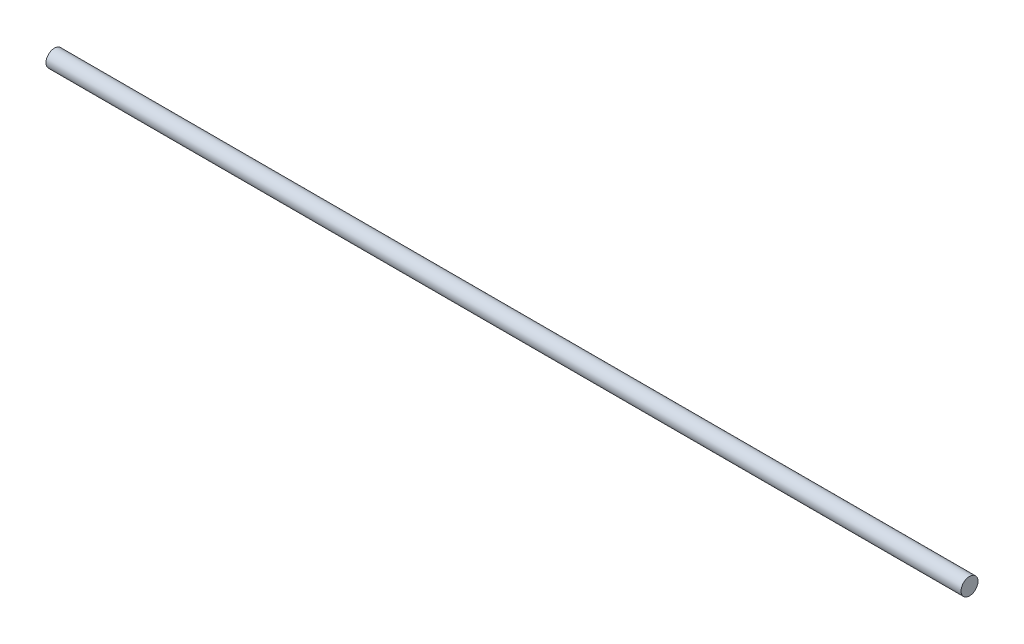
SolidWorks part; units mm, degrees
ref_plane "Front Plane" through (0, 0, 0) normal (0, 0, 1) x (1, 0, 0)
ref_plane "Top Plane" through (0, 0, 0) normal (0, 1, 0) x (1, 0, 0)
ref_plane "Right Plane" through (0, 0, 0) normal (1, 0, 0) x (0, 0, -1)
sketch "Sketch1" plane through (0, 0, 0) normal (1, 0, 0) x (0, 0, -1)
  circle A0 centre (0, 0) radius 5
  dimension "D1" = 10
extrude "Boss-Extrude1" add sketch "Sketch1" along normal blind 540
